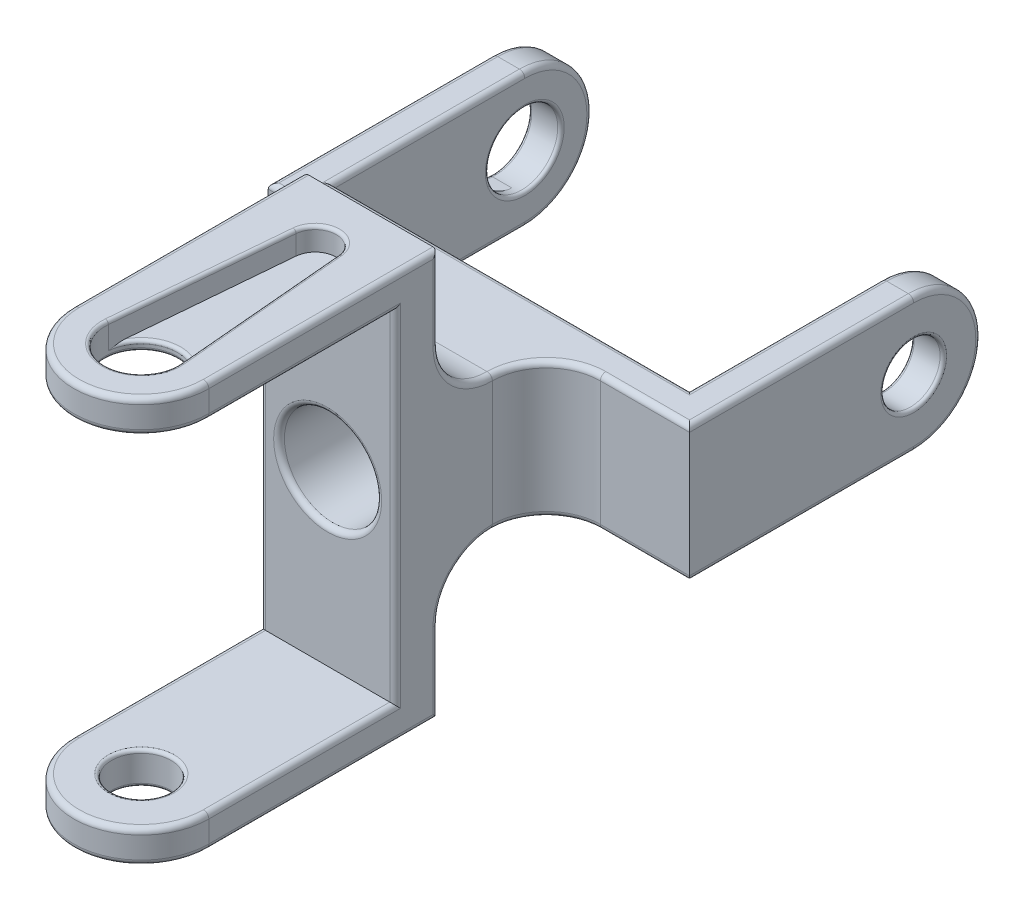
SolidWorks part; units mm, degrees
material "聚脂树脂"
ref_plane "前视基准面" through (0, 0, 0) normal (0, 0, 1) x (1, 0, 0)
ref_plane "上视基准面" through (0, 0, 0) normal (0, 1, 0) x (1, 0, 0)
ref_plane "右视基准面" through (0, 0, 0) normal (1, 0, 0) x (0, 0, -1)
sketch "草图1" plane through (0, 0, 0) normal (0, 0, 1) x (1, 0, 0)
  line L1 (-6.25, -18.75) -> (6.25, -18.75)
  line L2 (-6.25, -18.75) -> (-6.25, 18.75)
  line L3 (-6.25, 18.75) -> (6.25, 18.75)
  line L4 (6.25, -18.75) -> (6.25, 18.75)
  line L5 (-6.25, -18.75) -> (6.25, 18.75) construction
  line L6 (-6.25, 18.75) -> (6.25, -18.75) construction
  point P0 (0, 0)
  dimension "D1" = 12.5
  dimension "D2" = 37.5
extrude "凸台-拉伸1" add sketch "草图1" along normal blind 4
sketch "草图2" plane through (0, 0, 4) normal (0, 0, 1) x (1, 0, 0)
  line L0 (6.25, -18.75) -> (6.25, 18.75) construction
  line L1 (-6.25, 18.75) -> (6.25, 18.75)
  line L2 (-6.25, 18.75) -> (-6.25, 15.75)
  line L3 (-6.25, 15.75) -> (6.25, 15.75)
  line L4 (6.25, 18.75) -> (6.25, 15.75)
  line L5 (-6.25, 18.75) -> (-6.25, -18.75) construction
  line L6 (-6.25, -15.75) -> (6.25, -15.75)
  line L7 (-6.25, -15.75) -> (-6.25, -18.75)
  line L8 (-6.25, -18.75) -> (6.25, -18.75)
  line L9 (6.25, -15.75) -> (6.25, -18.75)
  dimension "D1" = 3
  dimension "D2" = 3
extrude "凸台-拉伸2" add sketch "草图2" along normal blind 17.25
sketch "草图5" plane through (0, 18.75, 0) normal (0, 1, 0) x (1, 0, 0)
  line L0 (6.25, -21.25) -> (-6.25, -21.25) construction
  circle A0 centre (0, -21.25) radius 6.25
extrude "凸台-拉伸3" add sketch "草图5" against normal blind 3
sketch "草图6" plane through (0, -18.75, 0) normal (0, -1, 0) x (1, 0, 0)
  line L0 (-6.25, 21.25) -> (6.25, 21.25) construction
  circle A0 centre (0, 21.25) radius 6.25
extrude "凸台-拉伸4" add sketch "草图6" against normal blind 3
sketch "草图7" plane through (0, 0, 0) normal (0, 0, -1) x (-1, 0, 0)
  line L0 (6.25, 18.75) -> (6.25, -18.75) construction
  line L1 (-6.25, -6.25) -> (6.25, -6.25)
  line L2 (-6.25, -6.25) -> (-6.25, 6.25)
  line L3 (-6.25, 6.25) -> (6.25, 6.25)
  line L4 (6.25, -6.25) -> (6.25, 6.25)
  line L5 (-6.25, -6.25) -> (6.25, 6.25) construction
  line L6 (-6.25, 6.25) -> (6.25, -6.25) construction
  point P0 (0, 0)
  dimension "D1" = 12.5
extrude "凸台-拉伸5" add sketch "草图7" along normal blind 10
sketch "草图8" plane through (0, 0, -10) normal (0, 0, -1) x (-1, 0, 0)
  line L1 (-19.5, -6.25) -> (19.5, -6.25)
  line L2 (-19.5, -6.25) -> (-19.5, 6.25)
  line L3 (-19.5, 6.25) -> (19.5, 6.25)
  line L4 (19.5, -6.25) -> (19.5, 6.25)
  line L5 (-19.5, -6.25) -> (19.5, 6.25) construction
  line L6 (-19.5, 6.25) -> (19.5, -6.25) construction
  point P0 (0, 0)
  dimension "D1" = 12.5
  dimension "D2" = 39
extrude "凸台-拉伸6" add sketch "草图8" along normal blind 3
sketch "草图9" plane through (0, 0, -13) normal (0, 0, -1) x (-1, 0, 0)
  line L0 (-19.5, 6.25) -> (-19.5, -6.25) construction
  line L1 (-19.5, 6.25) -> (-16.5, 6.25)
  line L2 (-19.5, 6.25) -> (-19.5, -6.25)
  line L3 (-19.5, -6.25) -> (-16.5, -6.25)
  line L4 (-16.5, 6.25) -> (-16.5, -6.25)
  line L5 (-19.5, -6.25) -> (19.5, -6.25) construction
  line L6 (19.5, 6.25) -> (-19.5, 6.25) construction
  line L7 (19.5, -6.25) -> (16.5, -6.25)
  line L8 (19.5, -6.25) -> (19.5, 6.25)
  line L9 (19.5, 6.25) -> (16.5, 6.25)
  line L10 (16.5, -6.25) -> (16.5, 6.25)
  dimension "D1" = 3
  dimension "D2" = 3
extrude "凸台-拉伸7" add sketch "草图9" along normal blind 17.75
sketch "草图10" plane through (19.5, 0, 0) normal (1, 0, 0) x (0, 0, -1)
  line L0 (30.75, 6.25) -> (30.75, -6.25) construction
  circle A0 centre (30.75, 0) radius 6.25
extrude "凸台-拉伸8" add sketch "草图10" against normal blind 3
sketch "草图11" plane through (-19.5, 0, 0) normal (-1, 0, 0) x (0, 0, 1)
  line L0 (-30.75, -6.25) -> (-30.75, 6.25) construction
  circle A0 centre (-30.75, 0) radius 6.25
extrude "凸台-拉伸9" add sketch "草图11" against normal blind 3
fillet "圆角1" radius 5 4 edges at (0, -6.25, 0) (6.25, 0, -10) (0, 6.25, 0) (-6.25, 0, -10)
sketch "草图12" plane through (0, 18.75, 0) normal (0, 1, 0) x (1, 0, 0)
  line L1 (-1.9426, -4.9804) -> (-3.3373, -20.9587)
  line L2 (3.3373, -20.9587) -> (1.9426, -4.9804)
  arc A0 (-3.3373, -20.9587) -> (3.3373, -20.9587) centre (0, -21.25) ccw
  arc A1 (1.9426, -4.9804) -> (-1.9426, -4.9804) centre (0, -5.15) ccw
  dimension "D1" = 6.7
  dimension "D2" = 3.9
  dimension "D3" = 16.1
extrude "切除-拉伸1" cut sketch "草图12" against normal blind 2.1
sketch "草图13" plane through (0, 16.65, 0) normal (0, 1, 0) x (1, 0, 0)
  circle A0 centre (0, -21.25) radius 3.35
extrude "切除-拉伸2" cut sketch "草图13" against normal up to next
sketch "草图14" plane through (0, -15.75, 0) normal (0, 1, 0) x (1, 0, 0)
  circle A0 centre (0, -21.25) radius 2.75
  dimension "D1" = 5.5
extrude "切除-拉伸3" cut sketch "草图14" against normal up to next
sketch "草图15" plane through (-19.5, 0, 0) normal (-1, 0, 0) x (0, 0, 1)
  line L0 (-30.4569, 3.3372) -> (-14.5794, 1.9425)
  line L1 (-30.4569, -3.3372) -> (-14.5794, -1.9425)
  arc A0 (-30.4569, 3.3372) -> (-30.4569, -3.3372) centre (-30.75, 0) ccw
  arc A1 (-14.5794, -1.9425) -> (-14.5794, 1.9425) centre (-14.75, 0) ccw
  dimension "D1" = 6.7
  dimension "D2" = 3.9
  dimension "D3" = 16
extrude "切除-拉伸4" cut sketch "草图15" against normal blind 2.1
sketch "草图16" plane through (-17.4, 0, 0) normal (-1, 0, 0) x (0, 0, 1)
  circle A0 centre (-30.75, 0) radius 3.35
extrude "切除-拉伸5" cut sketch "草图16" against normal up to next
sketch "草图17" plane through (19.5, 0, 0) normal (1, 0, 0) x (0, 0, -1)
  circle A0 centre (30.75, 0) radius 2.75
  dimension "D1" = 5.5
extrude "切除-拉伸6" cut sketch "草图17" against normal up to next
fillet "圆角2" radius 0.5 36 edges at (15.375, 6.25, -10) (7.7145, 6.25, -8.5355) (15.375, -6.25, -10) (7.7145, -6.25, -8.5355) (0, 18.75, 27.5) (0, 15.75, 27.5) (0, -15.75, 27.5) (0, -18.75, 27.5) (-15.375, -6.25, -10) (-7.7145, -6.25, -8.5355) (-15.375, 6.25, -10) (-7.7145, 6.25, -8.5355) (-19.5, 6.25, -20.375) (-19.5, -6.25, -20.375) (19.5, 6.25, -20.375) (19.5, 0, -37) (6.25, -18.75, 10.625) (6.25, -15.75, 12.625) (6.25, 0, 4) (6.25, 15.75, 12.625) (6.25, 18.75, 10.625) (6.25, 15, 0) (6.25, 7.7145, -1.4645) (6.25, -7.7145, -1.4645) (6.25, -15, 0) (-6.25, 18.75, 10.625) (-6.25, 15.75, 12.625) (-6.25, 0, 4) (-6.25, -15.75, 12.625) (-6.25, -18.75, 10.625) (-6.25, -15, 0) (-6.25, -7.7145, -1.4645) (-6.25, 7.7145, -1.4645) (-6.25, 15, 0) (-19.5, 0, -37) (19.5, -6.25, -20.375)
fillet "圆角3" radius 0.5 8 edges at (-16.5, 6.25, -21.875) (-16.5, 0, -37) (16.5, 6.25, -21.875) (16.5, 0, -37) (-16.5, -6.25, -21.875) (16.5, -6.25, -21.875) (0, -6.25, -13) (0, 6.25, -13)
fillet "圆角4" radius 0.3 15 edges at (-2.64, 18.75, 12.9696) (0, 18.75, 3.2) (2.64, 18.75, 12.9696) (-19.5, 2.6398, -22.5181) (-19.5, 0, -12.8) (-19.5, -2.6398, -22.5181) (0, 15.75, 24.6) (0, 16.65, 17.9) (0, 18.75, 24.6) (-16.5, 0, -27.4) (-19.5, 0, -34.1) (0, -18.75, 24) (-2.75, -15.75, 21.25) (16.5, 2.75, -30.75) (19.5, 0, -33.5)
sketch "草图18" plane through (0, 0, 4) normal (0, 0, 1) x (1, 0, 0)
  circle A0 centre (0, 0) radius 4.5
  dimension "D1" = 9
extrude "切除-拉伸7" cut sketch "草图18" against normal through all
fillet "圆角5" radius 0.5 2 edges at (4.5, 0, -13) (4.5, 0, 4)
